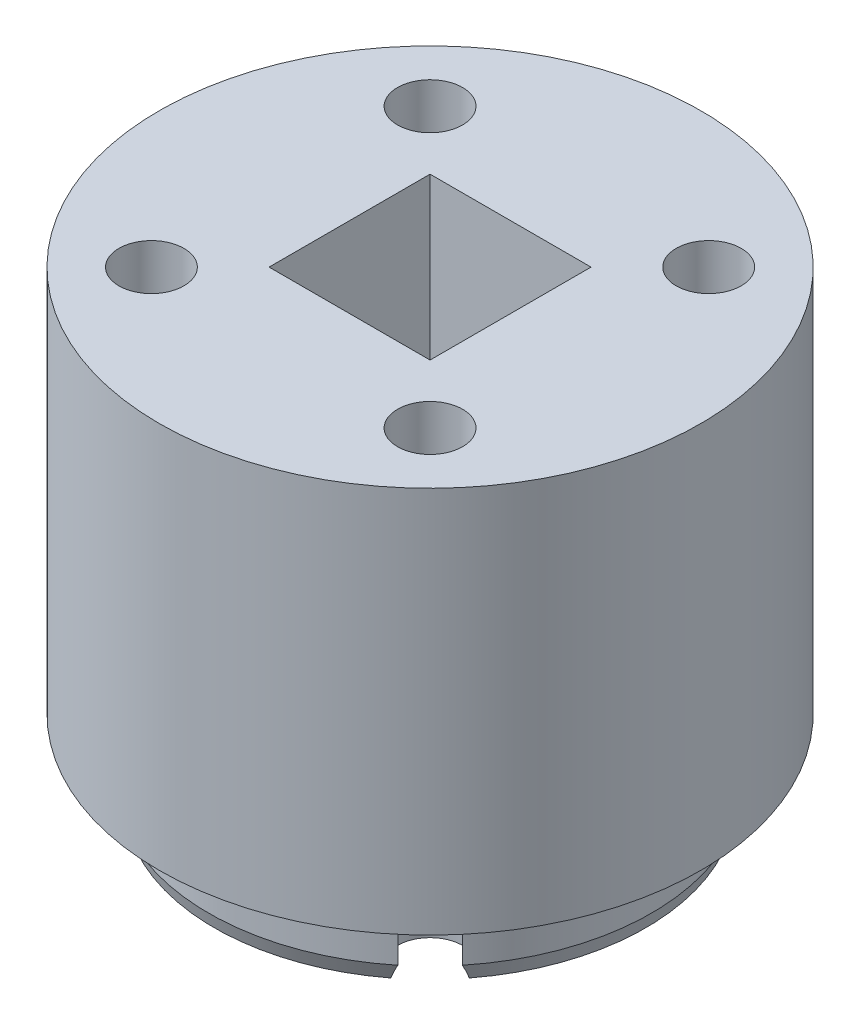
SolidWorks part; units mm, degrees
ref_plane "Спереди" through (0, 0, 0) normal (0, 0, 1) x (1, 0, 0)
ref_plane "Сверху" through (0, 0, 0) normal (0, 1, 0) x (1, 0, 0)
ref_plane "Справа" through (0, 0, 0) normal (1, 0, 0) x (0, 0, -1)
sketch "Sketch1" plane through (0, 0, 0) normal (0, 1, 0) x (1, 0, 0)
  circle A0 centre (0, 0) radius 17.5
  dimension "D1" = 35
extrude "Boss-Extrude1" add sketch "Sketch1" along normal blind 25
sketch "Sketch3" plane through (0, 0, 0) normal (0, -1, 0) x (1, 0, 0)
  circle A0 centre (0, 0) radius 14.3
  circle A1 centre (0, 0) radius 17.5 construction
  dimension "D1" = 3.2
extrude "Boss-Extrude2" add sketch "Sketch3" along normal blind 5
sketch "Sketch4" plane through (0, 25, 0) normal (0, 1, 0) x (1, 0, 0)
  line L1 (-5.2, 5.2) -> (5.2, 5.2)
  line L2 (-5.2, 5.2) -> (-5.2, -5.2)
  line L3 (-5.2, -5.2) -> (5.2, -5.2)
  line L4 (5.2, 5.2) -> (5.2, -5.2)
  line L5 (-5.2, 5.2) -> (5.2, -5.2) construction
  line L6 (-5.2, -5.2) -> (5.2, 5.2) construction
  point P0 (0, 0)
  dimension "D1" = 10.4
extrude "Cut-Extrude1" cut sketch "Sketch4" against normal through all
sketch "Sketch6" plane through (0, 25, 0) normal (0, 1, 0) x (1, 0, 0)
  line L1 (-9, 9) -> (9, 9) construction
  line L2 (-9, 9) -> (-9, -9) construction
  line L3 (-9, -9) -> (9, -9) construction
  line L4 (9, 9) -> (9, -9) construction
  line L5 (-9, 9) -> (9, -9) construction
  line L6 (-9, -9) -> (9, 9) construction
  circle A0 centre (9, -9) radius 2.1
  circle A1 centre (-9, -9) radius 2.1
  circle A2 centre (-9, 9) radius 2.1
  circle A3 centre (9, 9) radius 2.1
  point P0 (0, 0)
  dimension "D1" = 4.2
  dimension "D2" = 18
extrude "Cut-Extrude2" cut sketch "Sketch6" against normal through all
chamfer "Chamfer1" distance 1 angle 20 4 edges at (14.3, -5, 0) (0, -5, -14.3) (-14.3, -5, 0) (0, -5, 14.3) first distance on face at (12.7, -2.5, 0) first distance on face at (0, -2.5, -12.7) first distance on face at (-12.7, -2.5, 0) first distance on face at (0, -2.5, 12.7)
